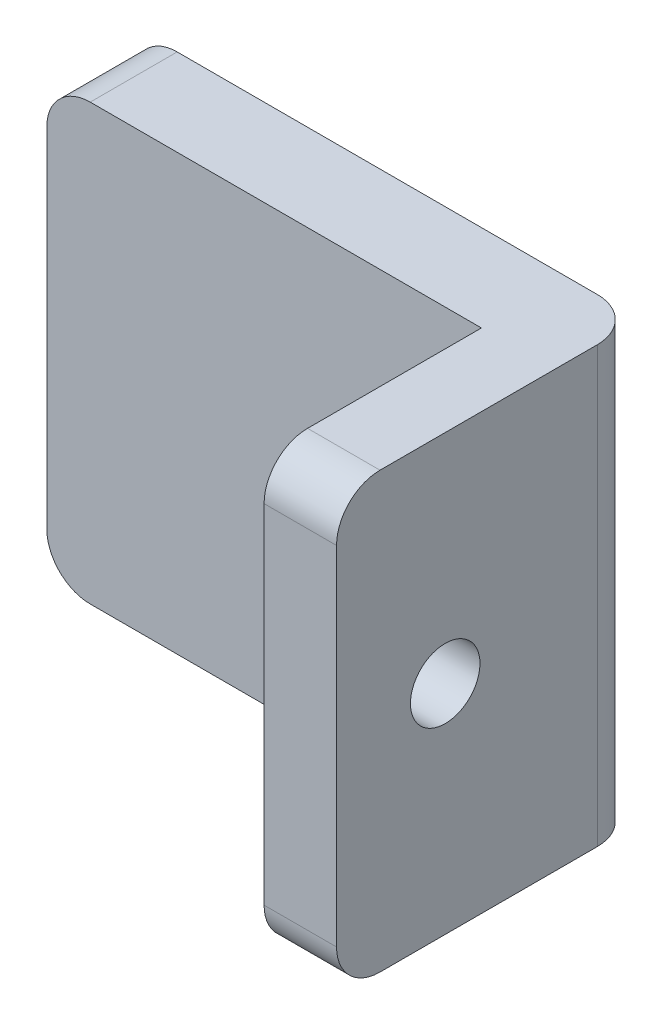
SolidWorks part; units mm, degrees
ref_plane "Front Plane" through (0, 0, 0) normal (0, 0, 1) x (1, 0, 0)
ref_plane "Top Plane" through (0, 0, 0) normal (0, 1, 0) x (1, 0, 0)
ref_plane "Right Plane" through (0, 0, 0) normal (1, 0, 0) x (0, 0, -1)
sketch "Sketch1" plane through (0, 0, 0) normal (0, 0, 1) x (1, 0, 0)
  line L0 (-266.5, -68.8259) -> (-266.5, -28.8259) construction
  line L1 (-271.5, -33) -> (-236.5, -33)
  line L2 (-271.5, -33) -> (-271.5, -63)
  line L3 (-271.5, -63) -> (-236.5, -63)
  line L4 (-236.5, -33) -> (-236.5, -63)
  dimension "D1" = 5
  dimension "D2" = 35
  dimension "D4" = 30
extrude "Boss-Extrude1" add sketch "Sketch1" along normal blind 6
sketch "Sketch3" plane through (0, 0, 6) normal (0, 0, 1) x (1, 0, 0)
  line L1 (-236.5, -63) -> (-241.5, -63)
  line L2 (-236.5, -63) -> (-236.5, -33)
  line L3 (-236.5, -33) -> (-241.5, -33)
  line L4 (-241.5, -63) -> (-241.5, -33)
extrude "Boss-Extrude2" add sketch "Sketch3" along normal blind 15
sketch "Sketch4" plane through (-236.5, 0, 0) normal (1, 0, 0) x (0, 0, -1)
  line L0 (-21, -48) -> (0, -48) construction
  line L1 (-21, -63) -> (-21, -33) construction
  line L2 (0, -63) -> (0, -33) construction
  circle A0 centre (-13.5, -48) radius 2.4
extrude "Cut-Extrude1" cut sketch "Sketch4" against normal up to surface (5 mm away) up to face at (-241.5, -48, 13.5)
fillet "Fillet1" radius 3 4 edges at (-271.5, -33, 3) (-271.5, -63, 3) (-239, -33, 21) (-239, -63, 21)
fillet "Fillet2" radius 3 1 edges at (-236.5, -48, 0)
